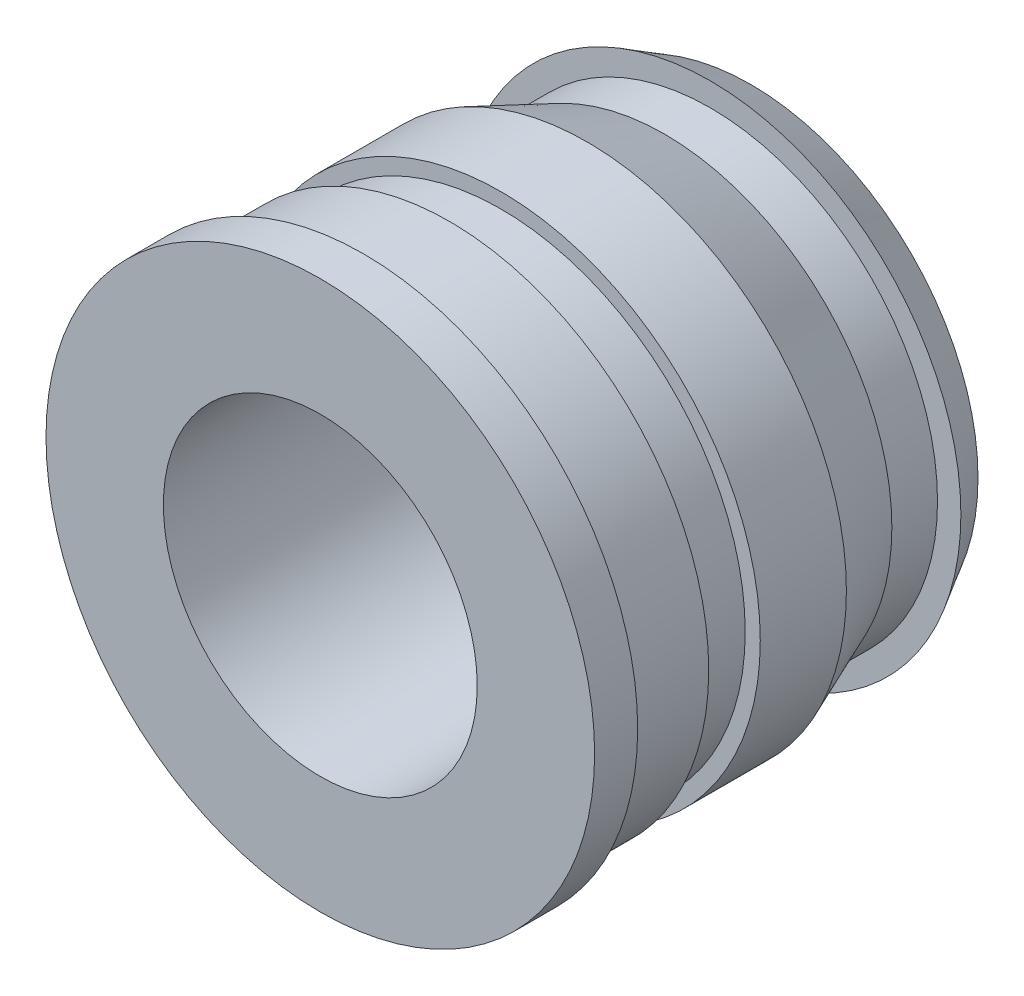
SolidWorks part; units mm, degrees
ref_plane "Front Plane" through (0, 0, 0) normal (0, 0, 1) x (1, 0, 0)
ref_plane "Top Plane" through (0, 0, 0) normal (0, 1, 0) x (1, 0, 0)
ref_plane "Right Plane" through (0, 0, 0) normal (1, 0, 0) x (0, 0, -1)
sketch "Sketch1" plane through (0, 0, 0) normal (1, 0, 0) x (0, 0, -1)
  line L0 (-1.715, 0) -> (1.715, 0) construction
  line L1 (-1.715, 1.25) -> (-1.715, 2.185)
  line L2 (-1.715, 2.185) -> (-1.372, 2.185)
  line L3 (-1.372, 2.185) -> (-1.372, 2.065)
  line L4 (-1.372, 2.065) -> (-0.686, 2.065)
  line L5 (-0.686, 2.065) -> (-0.686, 1.945)
  line L6 (-0.686, 1.945) -> (-0.2754, 1.945)
  line L7 (-0.2754, 1.945) -> (-0.2754, 2.065)
  line L9 (0.4106, 2.065) -> (1.029, 1.8088)
  line L13 (1.029, 1.8088) -> (1.3926, 1.8088)
  line L14 (1.3926, 1.8088) -> (1.3926, 1.995)
  line L15 (1.3926, 1.995) -> (1.715, 1.8088)
  line L16 (1.715, 1.8088) -> (1.715, 1.25)
  line L17 (-1.715, 1.995) -> (1.715, 1.995) construction
  line L18 (1.715, 0) -> (1.715, 1.995) construction
  line L19 (-1.715, 0) -> (-1.715, 2.185) construction
  line L20 (-0.2754, 2.065) -> (0.4106, 2.065)
  line L21 (-1.715, 1.25) -> (1.715, 1.25)
  line L23 (-2.1369, 1.2987) -> (-1.9119, 0.909) construction
  line L24 (-1.715, -1.995) -> (1.715, -1.995) construction
  line L25 (-1.9119, 0.909) -> (-1.6869, 1.2987) construction
  line L26 (-1.6869, 1.2987) -> (-2.1369, 1.2987) construction
  line L27 (-2.1088, 1.25) -> (-1.715, 1.25) construction
  line L28 (-1.9119, 1.2987) -> (-1.9119, 1.25) construction
  line L29 (-1.9119, 1.25) -> (-1.9119, 0.9577) construction
  line L30 (-1.9119, 0.9577) -> (-1.9119, 0.909) construction
  line L31 (-1.94, 0.9577) -> (-1.8838, 0.9577)
  line L32 (-2.1228, 1.2744) -> (-1.7009, 1.2744)
  line L33 (-1.8838, 0.9577) -> (-1.7009, 1.2744)
  line L34 (-1.94, 0.9577) -> (-2.1228, 1.2744)
  line L35 (-1.715, 1.945) -> (1.715, 1.945) construction
  line L36 (-1.715, -1.945) -> (1.715, -1.945) construction
  point P36 (-1.9119, 1.2744)
  dimension "Installed Length" = 3.43
  dimension "Dia A" = 4.37
  dimension "Dia B" = 3.99
  dimension "Thread Dia" = 2.5
  dimension "D6" = 30
  dimension "D8" = 0.686
  dimension "D4" = 22.5
  dimension "Thread Pitch" = 0.45
  dimension "D2" = 0.0563
  dimension "Max Hole Dia" = 3.89
  dimension "Knurling Length" = 2.401
  dimension "D1" = 3.6177
  dimension "D3" = 0.343
ref_plane "Plane1" through (0, 0, 1.372) normal (0, 0, 1) x (1, 0, 0)
sketch "Sketch2" plane through (0, 0, 1.372) normal (0, 0, 1) x (1, 0, 0)
  line L0 (0, 0) -> (0, 2.065) construction
  line L1 (-0.1556, 2.0692) -> (0, 1.945)
  line L2 (0.1556, 2.0692) -> (0, 1.945)
  line L3 (-0.144, 2.06) -> (0, 0) construction
  line L4 (0.144, 2.06) -> (0, 0) construction
  line L5 (0, 0) -> (-0.2695, 2.0473) construction
  line L6 (0, 0) -> (0.2695, 2.0473) construction
  line L7 (0, 0) -> (1.4602, 1.4602) construction
  line L8 (0, 0) -> (0, -1.2987) construction
  line L9 (0, 0) -> (0.6494, -1.1247) construction
  circle A0 centre (0, 0) radius 1.945 construction
  circle A1 centre (0, 0) radius 2.065 construction
  circle A3 centre (0, 0) radius 1.2987
  arc A4 (-0.1556, 2.0692) -> (0.1556, 2.0692) centre (0, 0) cw
  dimension "Knurl Angle" = 8
  dimension "Pattern Angle" = 15
  dimension "Helix Angle" = 45
  dimension "D1" = 30
sketch "Sketch3" plane through (0, 0, 0) normal (1, 0, 0) x (0, 0, -1)
  line L0 (-1.715, 1.25) -> (-1.715, 2.185) construction
  line L1 (-1.715, 2.185) -> (-1.372, 2.185) construction
  line L2 (-1.372, 2.185) -> (-1.372, 2.065) construction
  line L3 (-1.372, 2.065) -> (-0.686, 2.065) construction
  line L4 (-0.686, 2.065) -> (-0.686, 1.945) construction
  line L5 (-0.686, 1.945) -> (-0.2754, 1.945) construction
  line L6 (-0.2754, 1.945) -> (-0.2754, 2.065) construction
  line L8 (0.4106, 2.065) -> (1.029, 1.8088) construction
  line L12 (1.029, 1.8088) -> (1.3926, 1.8088) construction
  line L13 (1.3926, 1.8088) -> (1.3926, 1.995) construction
  line L14 (1.3926, 1.995) -> (1.715, 1.8088) construction
  line L15 (1.715, 1.8088) -> (1.715, 1.25) construction
  line L16 (-1.715, 1.25) -> (1.715, 1.25) construction
  line L17 (-1.715, 1.25) -> (-1.715, 2.185)
  line L18 (-1.715, 2.185) -> (-1.372, 2.185)
  line L19 (-1.372, 2.185) -> (-1.372, 2.065)
  line L20 (-1.372, 2.065) -> (-0.686, 2.065)
  line L21 (-0.686, 2.065) -> (-0.686, 1.945)
  line L22 (-0.686, 1.945) -> (-0.2754, 1.945)
  line L23 (-0.2754, 1.945) -> (-0.2754, 2.065)
  line L25 (0.4106, 2.065) -> (1.029, 1.8088)
  line L29 (1.029, 1.8088) -> (1.3926, 1.8088)
  line L30 (1.3926, 1.8088) -> (1.3926, 1.995)
  line L31 (1.3926, 1.995) -> (1.715, 1.8088)
  line L32 (1.715, 1.8088) -> (1.715, 1.25)
  line L33 (-1.715, 1.25) -> (1.715, 1.25)
  line L34 (-0.2754, 2.065) -> (0.4106, 2.065) construction
  line L35 (-0.2754, 2.065) -> (0.4106, 2.065)
revolve "Revolve1" add sketch "Sketch3" angle 360 about L0
sketch "Sketch4" [suppressed] plane through (0, 0, 1.372) normal (0, 0, 1) x (1, 0, 0)
  circle A2 centre (0, 0) radius 2.065 construction
  circle A3 centre (0, 0) radius 2.065
sketch "Sketch6" [suppressed] plane through (0, 0, 1.715) normal (0, 0, 1) x (1, 0, 0)
  circle A0 centre (0, 0) radius 1.25
curve "Helix/Spiral2" [suppressed] pitch 0.45 height 3.88 turns 8.6222
sketch "Sketch7" [suppressed] plane through (0, 0, 0) normal (1, 0, 0) x (0, 0, -1)
  line L0 (-1.94, 0.9577) -> (-1.8838, 0.9577) construction
  line L1 (-1.94, 0.9577) -> (-2.1228, 1.2744) construction
  line L2 (-2.1228, 1.2744) -> (-1.7009, 1.2744) construction
  line L3 (-1.8838, 0.9577) -> (-1.7009, 1.2744) construction
  line L4 (-1.94, 0.9577) -> (-1.8838, 0.9577)
  line L5 (-1.94, 0.9577) -> (-2.1228, 1.2744)
  line L6 (-2.1228, 1.2744) -> (-1.7009, 1.2744)
  line L7 (-1.8838, 0.9577) -> (-1.7009, 1.2744)
sweep "Sweep1" [suppressed] add profiles "Sketch7" path "Helix/Spiral2"
sketch "Sketch8" [suppressed] plane through (0, 0, 1.715) normal (0, 0, 1) x (1, 0, 0)
  circle A0 centre (0, 0) radius 1.2987
extrude "Cut-Extrude1" [suppressed] cut sketch "Sketch8" against normal through all draft 45 and the other way through all
mirror "Mirror1" [suppressed] about plane through (0, 0, 0) normal (0, 0, 1)
curve "Helix/Spiral1" [suppressed] pitch 19.208 height 2.401 turns 0.125
sketch "Sketch5" [suppressed] plane through (0, 0, 1.372) normal (0, 0, 1) x (1, 0, 0)
  line L0 (-0.1556, 2.0692) -> (0, 1.945) construction
  line L1 (0.1556, 2.0692) -> (0, 1.945) construction
  line L2 (-0.1556, 2.0692) -> (0, 1.945)
  line L3 (0.1556, 2.0692) -> (0, 1.945)
  arc A2 (0.1556, 2.0692) -> (-0.1556, 2.0692) centre (0, 0) ccw construction
  arc A3 (0.1556, 2.0692) -> (-0.1556, 2.0692) centre (0, 0) ccw
sweep "Cut-Sweep1" [suppressed] cut profiles "Sketch5" path "Helix/Spiral1"
pattern_circular "CirPattern1" [suppressed] count 24 over 360 about axis through (0, 0, 1.715) along (0, 0, -1) of bodies 105
equation "\"D8@Sketch1\"=\"Installed Length@Sketch1\" * .2"
equation "\"D4@Helix/Spiral1\"=\"Knurling Length@Sketch1\"*(360/\"Helix Angle@Sketch2\")"
equation "\"D3@Helix/Spiral1\"=\"Knurling Length@Sketch1\""
equation "\"D1@CirPattern1\"=\"D3@CirPattern1\"/\"Pattern Angle@Sketch2\""
equation "\"D2@Sketch1\" = \"Thread Pitch@Sketch1\" / 8"
equation "\"D4@Helix/Spiral2\"=\"Thread Pitch@Sketch1\""
equation "\"D3@Helix/Spiral2\" = \"Installed Length@Sketch1\" + \"Thread Pitch@Sketch1\""
equation "\"Knurling Length@Sketch1\"=\"Installed Length@Sketch1\" * .7"
equation "\"D1@Sketch1\"=\"Max Hole Dia@Sketch1\"*.93"
equation "\"D3@Sketch1\"=\"Installed Length@Sketch1\"*.1"
